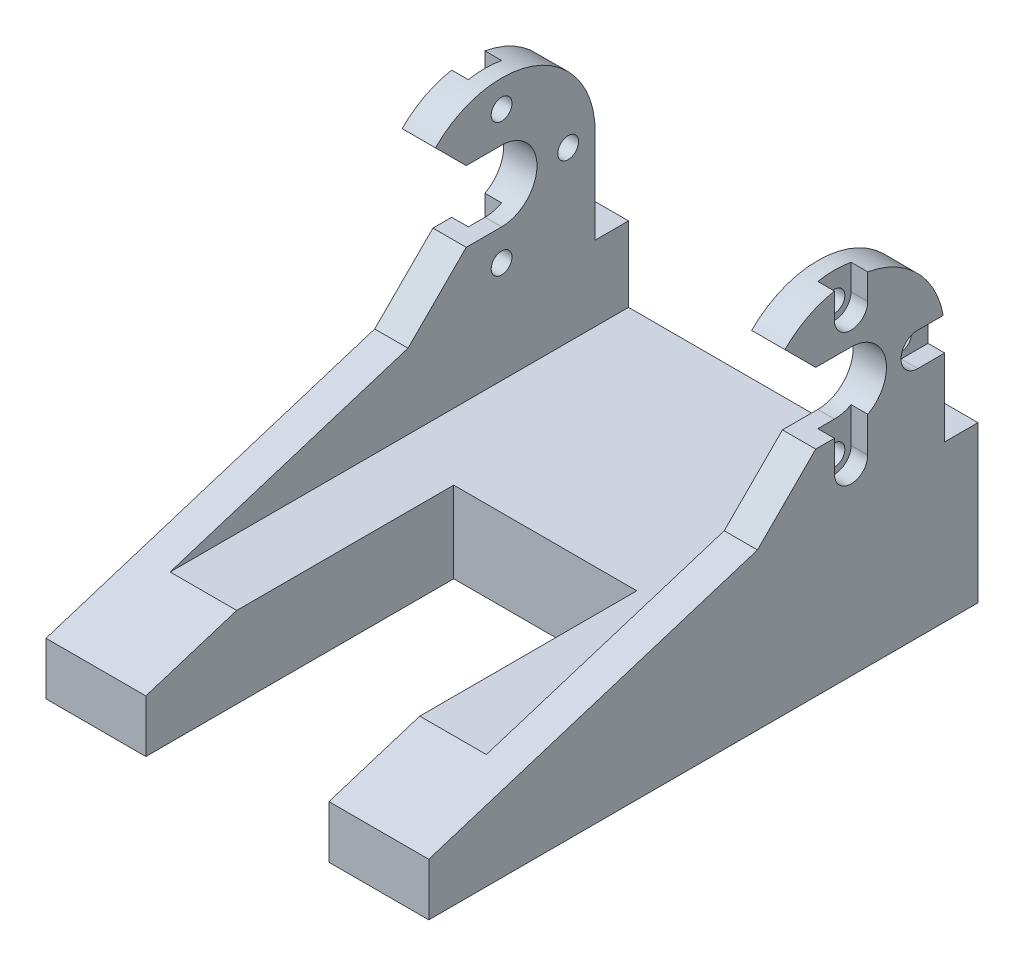
SolidWorks part; units mm, degrees
ref_plane "Front Plane" through (0, 0, 0) normal (0, 0, 1) x (1, 0, 0)
ref_plane "Top Plane" through (0, 0, 0) normal (0, 1, 0) x (1, 0, 0)
ref_plane "Right Plane" through (0, 0, 0) normal (1, 0, 0) x (0, 0, -1)
sketch "Sketch1" plane through (0, 0, 0) normal (0, 0, 1) x (1, 0, 0)
  line L1 (-25, 0) -> (25, 0)
  line L2 (-25, 0) -> (-25, -170)
  line L3 (-25, -170) -> (25, -170)
  line L4 (25, 0) -> (25, -170)
  dimension "D1" = 170
  dimension "D2" = 50
extrude "Boss-Extrude1" add sketch "Sketch1" against normal blind 55
sketch "Sketch2" plane through (0, 0, 0) normal (0, 0, 1) x (1, 0, 0)
  line L0 (25, 0) -> (-25, 0) construction
  line L1 (-17, 0) -> (17, 0)
  line L2 (-17, 0) -> (-17, -27)
  line L3 (-17, -27) -> (17, -27)
  line L4 (17, 0) -> (17, -27)
  line L5 (-25, 0) -> (-25, -170) construction
  dimension "D1" = 8
  dimension "D2" = 34
  dimension "D3" = 27
extrude "Cut-Extrude1" cut sketch "Sketch2" against normal through all
sketch "Sketch3" plane through (25, 0, 0) normal (1, 0, 0) x (0, 0, -1)
  line L0 (0, -170) -> (0, 0) construction
  line L1 (55, -27) -> (0, -27)
  line L2 (55, -27) -> (55, -24)
  line L3 (55, -24) -> (0, -24)
  line L4 (0, -27) -> (0, -24)
  line L5 (55, -170) -> (55, 0) construction
  line L7 (0, 0) -> (10, 0)
  line L8 (0, 0) -> (0, -24)
  line L9 (0, -24) -> (10, -24)
  line L10 (10, 0) -> (10, -24)
  line L11 (55, 0) -> (45, 0)
  line L12 (55, 0) -> (55, -24)
  line L13 (55, -24) -> (45, -24)
  line L14 (45, 0) -> (45, -24)
  circle A0 centre (27.5, -12.75) radius 10.25
  circle A1 centre (27.5, -12.75) radius 4.25
  circle A2 centre (27.5, -12.75) radius 8
  circle A3 centre (27.5, -4.75) radius 1
  circle A4 centre (35.5, -12.75) radius 1
  circle A5 centre (27.5, -20.75) radius 1
  circle A6 centre (19.5, -12.75) radius 1
  point P32 (27.5, -12.75)
  line M7 (0, 0) -> (0, -170)
  line M9 (55, -170) -> (55, 0)
  line M10 (55, 0) -> (0, 0)
  dimension "D2" = 11.25
  dimension "D3" = 27.5
  dimension "D4" = 20.5
  dimension "D7" = 8.5
  dimension "D8" = 16
  dimension "D9" = 4
  dimension "D1" = 3
  dimension "D5" = 10
  dimension "D6" = 10
extrude "Cut-Extrude2" cut sketch "Sketch3" against normal through all contours L14 L3 M10 M9 | L10 L3 M10 M7 | A2 A6 | A2 A6 | A1 | A2 A5 | A2 A5 | A2 A4 | A2 A4 | A2 A3 | A2 A3 region at (25, -12, -50) region at (25, -12, -5) region at (25, -12.75, -27.5) region at (25, -12.75, -35.0645) region at (25, -12.75, -35.913) region at (25, -5.1855, -27.5) region at (25, -4.337, -27.5) region at (25, -21.163, -27.5) region at (25, -20.3145, -27.5) region at (25, -12.75, -19.9355) region at (25, -12.75, -19.087)
sketch "Sketch4" plane through (0, 0, -10) normal (0, 0, 1) x (1, 0, 0)
  line L0 (-25, -24) -> (-17, -24) construction
  line L1 (-17, 0) -> (-19, 0)
  line L2 (-17, 0) -> (-17, -24)
  line L3 (-17, -24) -> (-19, -24)
  line L4 (-19, 0) -> (-19, -24)
  line L5 (0, 0) -> (0, -13.53) construction
  line L6 (19, 0) -> (19, -24)
  line L7 (17, -24) -> (19, -24)
  line L8 (17, 0) -> (17, -24)
  line L9 (17, 0) -> (19, 0)
  dimension "D1" = 2
extrude "Cut-Extrude3" cut sketch "Sketch4" against normal through all
sketch "Sketch5" plane through (25, 0, 0) normal (1, 0, 0) x (0, 0, -1)
  line L1 (10, 0) -> (45, 0)
  line L2 (10, 0) -> (10, -24)
  line L3 (10, -24) -> (45, -24)
  line L4 (45, 0) -> (45, -24)
  line L5 (38.75, -12.75) -> (38.75, -24)
  line L6 (16.25, -12.75) -> (10, -12.75)
  line L7 (16.25, -12.75) -> (16.25, -24)
  line L8 (16.25, -24) -> (10, -24)
  line L9 (10, -12.75) -> (10, -24)
  line L10 (38.75, -12.75) -> (45, -12.75)
  line L11 (38.75, -12.75) -> (38.75, -24)
  line L12 (38.75, -24) -> (45, -24)
  line L13 (45, -12.75) -> (45, -24)
  circle A0 centre (27.5, -12.75) radius 11.25
  line M8 (45, -24) -> (45, 0)
  line M9 (45, 0) -> (10, 0)
  line M10 (10, 0) -> (10, -24)
  dimension "D1" = 22.5
extrude "Cut-Extrude4" cut sketch "Sketch5" against normal through all contours A0 L10 L4 L6 M9 M10 | L7 L6 L2 L3 | L10 L5 L3 M8 region at (25, -0.3725, -27.5) region at (25, -18.375, -13.125) region at (25, -18.375, -41.875)
sketch "Sketch6" plane through (0, 0, 0) normal (0, 0, 1) x (1, 0, 0)
  line L1 (-19, -24) -> (19, -24)
  line L2 (-19, -24) -> (-19, -34)
  line L3 (-19, -34) -> (19, -34)
  line L4 (19, -24) -> (19, -34)
  dimension "D1" = 10
extrude "Cut-Extrude5" cut sketch "Sketch6" against normal through all
sketch "Sketch8" plane through (25, 0, 0) normal (1, 0, 0) x (0, 0, -1)
  line L0 (55, -170) -> (55, -24) construction
  line L1 (0, -170) -> (0, -24) construction
  line L2 (41.75, -132.5) -> (13.25, -132.5)
  line L3 (27.5, -132.5) -> (27.5, -179)
  line L4 (41.75, -179) -> (13.25, -179)
  line L5 (13.25, -132.5) -> (13.25, -179)
  line L7 (41.75, -132.5) -> (41.75, -179)
  line L11 (27.5, -167.75) -> (55, -167.75)
  line L12 (27.5, -167.75) -> (27.5, -170)
  line L13 (27.5, -170) -> (55, -170)
  line L14 (55, -167.75) -> (55, -170)
  line L16 (27.5, -167.75) -> (0, -167.75)
  line L17 (27.5, -167.75) -> (27.5, -170)
  line L18 (27.5, -170) -> (0, -170)
  line L19 (0, -167.75) -> (0, -170)
  circle A0 centre (27.5, -167.75) radius 10.25
  circle A1 centre (27.5, -12.75) radius 10.25
  line M4 (0, -24) -> (0, -170)
  line M5 (0, -170) -> (55, -170)
  line M6 (55, -170) -> (55, -24)
  dimension "D1" = 27.5
  dimension "D2" = 20.5
  dimension "D3" = 155
  dimension "D4" = 14.25
  dimension "D5" = 11.25
  dimension "D6" = 46.5
  dimension "D7" = 13.25
extrude "Cut-Extrude7" cut sketch "Sketch8" against normal through all contours A0 L3 L2 L5 L16 | A0 L11 L7 L2 L3 | L11 L7 M5 M6 | L5 L16 M4 M5 | A0 L16 L5 M5 | A0 L13 L7 L11 | L3 A0 L16 | L11 A0 L3 | L16 A0 L18 L3 | A0 L11 L3 M5 region at (25, -147.5157, -35.1704) region at (25, -147.5157, -19.8296) region at (25, -168.875, -48.375) region at (25, -168.8865, -39.7079) region at (25, -163.3998, -31.8502) region at (25, -163.3998, -23.1498) region at (25, -168.8704, -32.5838) region at (25, -168.8865, -15.2921) region at (25, -168.875, -6.625) region at (25, -168.8704, -22.4162)
sketch "Sketch9" plane through (0, 0, 0) normal (0, 0, 1) x (1, 0, 0)
  line L0 (-25, -167.75) -> (25, -167.75) construction
  line L1 (17, -167.75) -> (-17, -167.75)
  line L2 (17, -167.75) -> (17, -132.5)
  line L3 (17, -132.5) -> (-17, -132.5)
  line L4 (-17, -167.75) -> (-17, -132.5)
  line L5 (-25, -132.5) -> (25, -132.5) construction
  line L7 (-25, -24) -> (-25, -167.75) construction
  line L9 (25, -167.75) -> (25, -24) construction
  dimension "D1" = 8
  dimension "D2" = 8
extrude "Cut-Extrude8" cut sketch "Sketch9" against normal through all
sketch "Sketch11" plane through (25, 0, 0) normal (1, 0, 0) x (0, 0, -1)
  line L0 (27.5, -157.5) -> (27.5, -147.5)
  line L2 (27.5, -147.5) -> (55, -147.5)
  line L3 (27.5, -147.5) -> (27.5, -167.75)
  line L4 (27.5, -167.75) -> (55, -167.75)
  line L5 (55, -147.5) -> (55, -167.75)
  line L6 (27.5, -147.5) -> (0, -147.5)
  line L7 (27.5, -147.5) -> (27.5, -167.75)
  line L8 (27.5, -167.75) -> (0, -167.75)
  line L9 (0, -147.5) -> (0, -167.75)
  circle A0 centre (27.5, -167.75) radius 10.25
  arc A1 (38.75, -12.75) -> (16.25, -12.75) centre (27.5, -12.75) ccw construction
  line M1 (0, -167.75) -> (13.25, -167.75)
  line M2 (13.25, -167.75) -> (13.25, -132.5)
  line M4 (41.75, -132.5) -> (41.75, -167.75)
  line M5 (41.75, -167.75) -> (55, -167.75)
  line M6 (55, -167.75) -> (55, -24)
  line M12 (0, -24) -> (0, -167.75)
  dimension "D1" = 155
  dimension "D2" = 20.5
  dimension "D3" = 10
extrude "Cut-Extrude9" cut sketch "Sketch11" against normal through all contours A0 L0 L6 L8 M2 | A0 L4 L2 L0 M4 | L2 M4 M5 M6 | L6 M2 M12 M1 region at (25, -155.3124, -19.2638) region at (25, -155.3124, -35.7362) region at (25, -157.625, -48.375) region at (25, -157.625, -6.625)
sketch "Sketch12" plane through (25, 0, 0) normal (1, 0, 0) x (0, 0, -1)
  line L1 (13.25, -132.5) -> (41.75, -132.5)
  line L2 (13.25, -132.5) -> (13.25, -147.5)
  line L3 (13.25, -147.5) -> (41.75, -147.5)
  line L4 (41.75, -132.5) -> (41.75, -147.5)
extrude "Boss-Extrude2" add sketch "Sketch12" against normal blind 8
ref_plane "Plane1" through (0, 0, 0) normal (1, 0, 0) x (0, 0, -1)
mirror "Mirror1" about plane through (0, 0, 0) normal (1, 0, 0) of "Boss-Extrude2"
sketch "Sketch14" plane through (0, 0, 0) normal (0, 0, 1) x (1, 0, 0)
  line L0 (17, -148.55) -> (17, -158.75) construction
  line L1 (-17, -132.5) -> (17, -132.5)
  line L2 (-17, -132.5) -> (-17, -147.5)
  line L3 (-17, -147.5) -> (17, -147.5)
  line L4 (17, -132.5) -> (17, -147.5)
  line L5 (-17, -147.5) -> (17, -147.5)
  line L6 (-17, -147.5) -> (-17, -157.75)
  line L7 (-17, -157.75) -> (17, -157.75)
  line L8 (17, -147.5) -> (17, -157.75)
  line M11 (-17, -147.5) -> (-17, -132.5)
  line M12 (-17, -132.5) -> (17, -132.5)
  line M13 (17, -132.5) -> (17, -147.5)
  dimension "D1" = 10.25
extrude "Boss-Extrude3" add sketch "Sketch14" against normal blind 13.25 contours L3 M11 M13 M12 | L8 L3 L6 L7 region at (0, -140, 0) region at (0, -152.625, 0)
ref_plane "Plane2" through (0, 0, -27.5) normal (0, 0, 1) x (1, 0, 0)
mirror "Mirror2" about plane through (0, 0, -27.5) normal (0, 0, 1) of "Boss-Extrude3"
sketch "Sketch16" plane through (25, 0, 0) normal (1, 0, 0) x (0, 0, -1)
  line L0 (41.75, -132.5) -> (13.25, -132.5) construction
  line L1 (13.25, -132.5) -> (13.25, -147.5) construction
  circle A1 centre (16.5, -135.75) radius 2.5
  circle A2 centre (16.5, -135.75) radius 4.5
  circle A3 centre (38.5, -135.75) radius 4.5
  dimension "D1" = 3.25
  dimension "D2" = 3.25
  dimension "D3" = 2
extrude "Cut-Extrude13" cut sketch "Sketch16" against normal blind 8 contours A1 | A2 A1 | A3 region at (25, -135.75, -16.5) region at (25, -135.75, -12.1273) region at (25, -135.75, -38.5)
mirror "Mirror3" about plane through (0, 0, 0) normal (1, 0, 0) of "Cut-Extrude13"
sketch "Sketch17" plane through (25, 0, 0) normal (1, 0, 0) x (0, 0, -1)
  line L0 (55, -147.5) -> (55, -24) construction
  line L1 (27.5, -1.5) -> (55, -1.5)
  line L2 (27.5, -1.5) -> (27.5, -51.5)
  line L3 (27.5, -51.5) -> (55, -51.5)
  line L4 (55, -1.5) -> (55, -51.5)
  line L8 (55, -51.5) -> (0, -51.5)
  line L9 (55, -51.5) -> (55, -157.75)
  line L10 (55, -157.75) -> (0, -157.75)
  line L11 (0, -51.5) -> (0, -157.75)
  arc A0 (38.75, -12.75) -> (16.25, -12.75) centre (27.5, -12.75) ccw construction
  circle M2 centre (16.5, -135.75) radius 4.5
  circle M3 centre (38.5, -135.75) radius 4.5
  line M4 (0, -147.5) -> (55, -147.5)
  line M5 (55, -147.5) -> (55, -24)
  line M11 (0, -24) -> (0, -147.5)
  dimension "D1" = 50
extrude "Cut-Extrude15" cut sketch "Sketch17" against normal through all contours L3 L8 M11 M4 M5 M2 M3 | L11 L10 L9 M4 | M3 | M2 region at (25, -98.6049, -27.5) region at (25, -152.625, -27.5) region at (25, -135.75, -16.5) region at (25, -135.75, -38.5)
sketch "Sketch18" plane through (25, 0, 0) normal (1, 0, 0) x (0, 0, -1)
  line L1 (38.75, -24) -> (-71.25, -24)
  line L2 (38.75, -24) -> (38.75, -51.5)
  line L3 (38.75, -51.5) -> (-71.25, -51.5)
  line L4 (-71.25, -24) -> (-71.25, -51.5)
  line L6 (38.75, -24) -> (68.75, -24)
  line L7 (38.75, -24) -> (38.75, -51.5)
  line L8 (38.75, -51.5) -> (68.75, -51.5)
  line L9 (68.75, -24) -> (68.75, -51.5)
  line M8 (0, -24) -> (0, -51.5)
  line M9 (0, -51.5) -> (55, -51.5)
  line M10 (55, -51.5) -> (55, -24)
  line M11 (55, -24) -> (38.75, -24)
  line M15 (16.25, -24) -> (0, -24)
  dimension "D1" = 110
  dimension "D2" = 30
extrude "Boss-Extrude4" add sketch "Sketch18" against normal blind 50 contours L1 L4 L3 M8 | L9 L6 L8 M10 | L2 L1 M15 M8 M9 | L2 M11 M9 M10 region at (25, -37.75, -19.375) region at (25, -37.75, -46.875) region at (25, -37.75, -61.875) region at (25, -37.75, 35.625)
sketch "Sketch19" plane through (0, 0, 71.25) normal (0, 0, 1) x (1, 0, 0)
  line L1 (-19, -24) -> (19, -24)
  line L2 (-19, -24) -> (-19, -31)
  line L3 (-19, -31) -> (19, -31)
  line L4 (19, -24) -> (19, -31)
  dimension "D1" = 7
extrude "Cut-Extrude16" cut sketch "Sketch19" against normal through all
sketch "Sketch20" plane through (25, 0, 0) normal (1, 0, 0) x (0, 0, -1)
  line L1 (-71.25, -24) -> (68.75, -24)
  line L2 (-71.25, -24) -> (-71.25, -51.5)
  line L3 (-71.25, -51.5) -> (68.75, -51.5)
  line L4 (68.75, -24) -> (68.75, -51.5)
  line L5 (16.25, -24) -> (-13.75, -24)
  line L6 (16.25, -24) -> (16.25, -51.5)
  line L7 (16.25, -51.5) -> (-13.75, -51.5)
  line L8 (-13.75, -24) -> (-13.75, -51.5)
  line L10 (-13.75, -51.5) -> (-71.25, -51.5)
  line L11 (-13.75, -51.5) -> (-13.75, -24)
  line L12 (-13.75, -24) -> (-71.25, -24)
  line L13 (-71.25, -51.5) -> (-71.25, -24)
  line M8 (-71.25, -24) -> (-71.25, -51.5)
  line M9 (-71.25, -51.5) -> (68.75, -51.5)
  dimension "D1" = 30
extrude "Cut-Extrude17" cut sketch "Sketch20" against normal through all contours L8 L1 M8 M9 region at (25, -37.75, 42.5)
sketch "Sketch21" plane through (25, 0, 0) normal (1, 0, 0) x (0, 0, -1)
  line L0 (16.25, -24) -> (-13.75, -51.5)
  line L1 (16.25, -24) -> (-13.75, -24)
  line L2 (16.25, -24) -> (16.25, -51.5)
  line L3 (16.25, -51.5) -> (-13.75, -51.5)
  line L4 (-13.75, -24) -> (-13.75, -51.5)
  line M6 (16.25, -24) -> (-13.75, -24)
  line M7 (-13.75, -24) -> (-13.75, -51.5)
extrude "Cut-Extrude18" cut sketch "Sketch21" against normal through all contours L0 M6 M7 region at (25, -33.1667, 3.75)
sketch "Sketch22" plane through (25, 0, 0) normal (1, 0, 0) x (0, 0, -1)
  line L3 (68.75, -51.5) -> (-13.75, -51.5)
  line L4 (68.75, -51.5) -> (68.75, -54)
  line L5 (68.75, -54) -> (-13.75, -54)
  line L6 (-13.75, -51.5) -> (-13.75, -54)
  dimension "D1" = 2.5
extrude "Boss-Extrude5" add sketch "Sketch22" against normal blind 50
sketch "Sketch24" plane through (25, 0, 0) normal (1, 0, 0) x (0, 0, -1)
  line L1 (68.75, -24) -> (46.75, -24)
  line L2 (68.75, -24) -> (68.75, -41)
  line L3 (68.75, -41) -> (46.75, -41)
  line L4 (46.75, -24) -> (46.75, -41)
  dimension "D1" = 17
  dimension "D2" = 22
extrude "Cut-Extrude19" cut sketch "Sketch24" against normal through all
sketch "Sketch25" plane through (0, -31, 0) normal (0, 1, 0) x (1, 0, 0)
  line L1 (-19, 46.75) -> (19, 46.75)
  line L2 (-19, 46.75) -> (-19, 8.6136)
  line L3 (-19, 8.6136) -> (19, 8.6136)
  line L4 (19, 46.75) -> (19, 8.6136)
extrude "Cut-Extrude20" cut sketch "Sketch25" against normal blind 10
sketch "Sketch27" plane through (0, -41, 0) normal (0, 1, 0) x (1, 0, 0)
  line L0 (-25, 68.75) -> (25, 68.75) construction
  line L1 (19, 8.6136) -> (-19, 8.6136)
  line L2 (19, 8.6136) -> (19, 68.75)
  line L3 (19, 68.75) -> (-19, 68.75)
  line L4 (-19, 8.6136) -> (-19, 68.75)
extrude "Boss-Extrude6" add sketch "Sketch27" along normal blind 8.6
sketch "Sketch29" plane through (0, 0, -8.6136) normal (0, 0, -1) x (-1, 0, 0)
  line L1 (-19, -31) -> (19, -31)
  line L2 (-19, -31) -> (-19, -32.4)
  line L3 (-19, -32.4) -> (19, -32.4)
  line L4 (19, -31) -> (19, -32.4)
extrude "Cut-Extrude21" cut sketch "Sketch29" against normal through all
sketch "Sketch30" plane through (-25, 0, 0) normal (-1, 0, 0) x (0, 0, 1)
  line L0 (-68.75, -32.4) -> (-68.75, -41) construction
  line L1 (-38.75, -24) -> (31.25, -24)
  line L2 (-38.75, -24) -> (-38.75, -53.9144)
  line L3 (-38.75, -53.9144) -> (31.25, -53.9144)
  line L4 (31.25, -24) -> (31.25, -53.9144)
  line L5 (-16.25, -24) -> (31.25, -38.9572)
  line L6 (31.25, -38.9572) -> (31.25, -53.9144)
  line L7 (-16.25, -24) -> (-16.25, -32.4)
  line L8 (-46.75, -32.4) -> (-7.0864, -32.4) construction
  line L9 (-16.25, -32.4) -> (-7.0864, -32.4)
  line L10 (-7.0864, -32.4) -> (-16.25, -24)
  line M5 (13.75, -54) -> (13.75, -51.5)
  line M6 (13.75, -51.5) -> (-16.25, -24)
  dimension "D1" = 100
extrude "Boss-Extrude7" add sketch "Sketch30" against normal blind 50 contours L5 L3 L4 M6 M5 | L7 L9 L10 region at (-25, -40.9436, 13.5151)
sketch "Sketch31" plane through (0, 0, -68.75) normal (0, 0, -1) x (-1, 0, 0)
  line L1 (-19, -24) -> (19, -24)
  line L2 (-19, -24) -> (-19, -41)
  line L3 (-19, -41) -> (19, -41)
  line L4 (19, -24) -> (19, -41)
extrude "Cut-Extrude22" cut sketch "Sketch31" against normal through all
sketch "Sketch32" plane through (25, 0, 0) normal (1, 0, 0) x (0, 0, -1)
  line L0 (-31.25, -38.9572) -> (-31.25, -53.9144) construction
  line L1 (68.75, -54) -> (-31.25, -54)
  line L2 (68.75, -54) -> (68.75, -51)
  line L3 (68.75, -51) -> (-31.25, -51)
  line L4 (-31.25, -54) -> (-31.25, -51)
  dimension "D1" = 3
extrude "Cut-Extrude23" cut sketch "Sketch32" against normal through all
sketch "Sketch33" plane through (0, -41, 0) normal (0, 1, 0) x (1, 0, 0)
  line L0 (19, -31.25) -> (-19, -31.25) construction
  line L1 (11, -31.25) -> (-11, -31.25)
  line L2 (11, -31.25) -> (11, 13.75)
  line L3 (11, 13.75) -> (-11, 13.75)
  line L4 (-11, -31.25) -> (-11, 13.75)
  line L6 (-25, 68.75) -> (-10, 68.75)
  line L7 (-25, 68.75) -> (-25, 46.75)
  line L8 (-25, 46.75) -> (-10, 46.75)
  line L9 (-10, 68.75) -> (-10, 46.75)
  line L10 (25, 68.75) -> (10, 68.75)
  line L11 (25, 68.75) -> (25, 46.75)
  line L12 (25, 46.75) -> (10, 46.75)
  line L13 (10, 68.75) -> (10, 46.75)
  line L15 (19, 16.25) -> (19, -31.25) construction
  line L16 (-19, -31.25) -> (-19, 46.75) construction
  line L18 (-10, 68.75) -> (10, 68.75)
  line L19 (-10, 68.75) -> (-10, 58.75)
  line L20 (-10, 58.75) -> (10, 58.75)
  line L21 (10, 68.75) -> (10, 58.75)
  line M10 (-25, 46.75) -> (-19, 46.75)
  line M12 (-19, -31.25) -> (19, -31.25)
  line M14 (19, 46.75) -> (25, 46.75)
  line M15 (25, 46.75) -> (25, 68.75)
  line M16 (25, 68.75) -> (-25, 68.75)
  line M17 (-25, 68.75) -> (-25, 46.75)
  dimension "D1" = 8
  dimension "D2" = 8
  dimension "D3" = 45
  dimension "D4" = 15
  dimension "D5" = 15
  dimension "D6" = 10
extrude "Cut-Extrude24" cut sketch "Sketch33" against normal through all contours L9 L8 M16 M17 M10 | L13 L12 M16 M14 M15 | L9 L20 L13 M16 | L4 L2 L3 M12 region at (0, -41, 8.75) region at (-17.5, -41, -57.75) region at (0, -41, -63.75) region at (17.5, -41, -57.75)
sketch "Sketch34" plane through (0, -41, 0) normal (0, 1, 0) x (1, 0, 0)
  line L0 (-10, 58.75) -> (10, 58.75) construction
  line L1 (-4, 58.75) -> (4, 58.75)
  line L2 (-4, 58.75) -> (-4, 46.75)
  line L3 (-4, 46.75) -> (4, 46.75)
  line L4 (4, 58.75) -> (4, 46.75)
  line L5 (-10, 58.75) -> (-10, 46.75) construction
  line L6 (10, 58.75) -> (10, 46.75) construction
  dimension "D1" = 6
  dimension "D2" = 6
  dimension "D3" = 12
extrude "Cut-Extrude25" cut sketch "Sketch34" against normal through all
sketch "Sketch36" plane through (0, -41, 0) normal (0, 1, 0) x (1, 0, 0)
  line L1 (19, -31.25) -> (-19, -31.25)
  line L2 (19, -31.25) -> (19, 58.75)
  line L3 (19, 58.75) -> (-19, 58.75)
  line L4 (-19, -31.25) -> (-19, 58.75)
  line L5 (-4, 58.75) -> (4, 58.75)
  line L6 (-4, 58.75) -> (-4, 46.75)
  line L7 (-4, 46.75) -> (4, 46.75)
  line L8 (4, 58.75) -> (4, 46.75)
  line L9 (10, 58.75) -> (19, 58.75)
  line L10 (10, 58.75) -> (10, 46.75)
  line L11 (10, 46.75) -> (19, 46.75)
  line L12 (19, 58.75) -> (19, 46.75)
  line L13 (-10, 58.75) -> (-19, 58.75)
  line L14 (-10, 58.75) -> (-10, 46.75)
  line L15 (-10, 46.75) -> (-19, 46.75)
  line L16 (-19, 58.75) -> (-19, 46.75)
  line L17 (-11, 13.75) -> (11, 13.75)
  line L18 (-11, 13.75) -> (-11, -31.25)
  line L19 (-11, -31.25) -> (11, -31.25)
  line L20 (11, 13.75) -> (11, -31.25)
  line M1 (4, 46.75) -> (-4, 46.75)
  line M2 (-4, 46.75) -> (-4, 58.75)
  line M3 (-4, 58.75) -> (-10, 58.75)
  line M4 (-10, 58.75) -> (-10, 46.75)
  line M5 (-10, 46.75) -> (-19, 46.75)
  line M6 (-19, 46.75) -> (-19, -31.25)
  line M7 (-19, -31.25) -> (-11, -31.25)
  line M8 (-11, -31.25) -> (-11, 13.75)
  line M9 (-11, 13.75) -> (11, 13.75)
  line M10 (11, 13.75) -> (11, -31.25)
  line M11 (11, -31.25) -> (19, -31.25)
  line M12 (19, -31.25) -> (19, 46.75)
  line M13 (19, 46.75) -> (10, 46.75)
  line M14 (10, 46.75) -> (10, 58.75)
  line M15 (10, 58.75) -> (4, 58.75)
  line M16 (4, 58.75) -> (4, 46.75)
extrude "Boss-Extrude8" add sketch "Sketch36" along normal blind 8 contours M16 M1 M2 M3 M4 M5 M6 M7 M8 M9 M10 M11 M12 M13 M14 M15 region at (0, -41, -18.522)
sketch "Sketch37" plane through (25, 0, 0) normal (1, 0, 0) x (0, 0, -1)
  line L0 (-31.25, -38.9572) -> (-31.25, -51) construction
  line L1 (58.75, -51) -> (-31.25, -51)
  line L2 (58.75, -51) -> (58.75, -42)
  line L3 (58.75, -42) -> (-31.25, -42)
  line L4 (-31.25, -51) -> (-31.25, -42)
  line L5 (-31.25, -38.9572) -> (-12.3315, -33)
  line L6 (-12.3315, -33) -> (-31.25, -33)
  line L7 (-12.3315, -33) -> (-12.3315, -38.9572)
  line L8 (-12.3315, -38.9572) -> (-31.25, -38.9572)
  line L9 (-31.25, -33) -> (-31.25, -38.9572)
  line L11 (58.75, -42) -> (46.75, -42)
  line L12 (58.75, -42) -> (58.75, -51)
  line L13 (58.75, -51) -> (46.75, -51)
  line L14 (46.75, -42) -> (46.75, -51)
  line M7 (-31.25, -51) -> (46.75, -51)
  line M8 (46.75, -51) -> (46.75, -24)
  line M13 (16.25, -24) -> (-31.25, -38.9572)
  line M14 (-31.25, -38.9572) -> (-31.25, -51)
  dimension "D1" = 9
extrude "Cut-Extrude27" cut sketch "Sketch37" against normal through all contours L3 M8 M14 M7 | L6 L9 M13 | L2 L3 L1 M8 region at (25, -34.9857, 24.9438) region at (25, -46.5, -52.75) region at (25, -46.5, -7.75)
fillet "Fillet1" radius 10 2 edges at (-7, -42, -58.75) (7, -42, -58.75)
sketch "Sketch38" plane through (0, 0, 0) normal (0, 1, 0) x (1, 0, 0)
  line L6 (-11, -31.25) -> (-25, -31.25) construction
  line L7 (-25, 46.75) -> (-23, 46.75)
  line L8 (-25, 46.75) -> (-25, -31.25)
  line L9 (-25, -31.25) -> (-23, -31.25)
  line L10 (-23, 46.75) -> (-23, -31.25)
  line L11 (25, -31.25) -> (11, -31.25) construction
  line L12 (25, 46.75) -> (23, 46.75)
  line L13 (25, 46.75) -> (25, -31.25)
  line L14 (25, -31.25) -> (23, -31.25)
  line L15 (23, 46.75) -> (23, -31.25)
  line L17 (-23, -31.25) -> (23, -31.25)
  line L18 (-23, -31.25) -> (-23, -23.25)
  line L19 (-23, -23.25) -> (23, -23.25)
  line L20 (23, -31.25) -> (23, -23.25)
  dimension "D1" = 2
  dimension "D2" = 2
  dimension "D3" = 8
extrude "Cut-Extrude29" cut sketch "Sketch38" against normal through all both and the other way through all contours L10 L7 L8 L9 | L12 L15 L14 L13 | L19 L10 L17 L15 region at (-24, 0, -7.75) region at (0, 0, 27.25) region at (24, 0, -7.75)
sketch "Sketch39" plane through (23, 0, 0) normal (1, 0, 0) x (0, 0, -1)
  line L0 (46.75, -24) -> (38.75, -24) construction
  line L1 (42.75, -24) -> (64.9734, -24)
  line L2 (42.75, -24) -> (42.75, -43.4413)
  line L3 (42.75, -43.4413) -> (64.9734, -43.4413)
  line L4 (64.9734, -24) -> (64.9734, -43.4413)
extrude "Cut-Extrude30" cut sketch "Sketch39" against normal through all
sketch "Sketch41" plane through (0, -42, 0) normal (0, -1, 0) x (1, 0, 0)
  line L1 (-23, 23.25) -> (23, 23.25)
  line L2 (-23, 23.25) -> (-23, -42.75)
  line L3 (-23, -42.75) -> (23, -42.75)
  line L4 (23, 23.25) -> (23, -42.75)
  line L5 (-11, 23.25) -> (11, 23.25)
  line L6 (-11, 23.25) -> (-11, -13.75)
  line L7 (-11, -13.75) -> (11, -13.75)
  line L8 (11, 23.25) -> (11, -13.75)
  line M1 (-23, 23.25) -> (-23, -42.75)
  line M2 (-23, -42.75) -> (23, -42.75)
  line M3 (23, -42.75) -> (23, 23.25)
  line M4 (23, 23.25) -> (11, 23.25)
  line M5 (11, 23.25) -> (11, -13.75)
  line M6 (11, -13.75) -> (-11, -13.75)
  line M7 (-11, -13.75) -> (-11, 23.25)
  line M8 (-11, 23.25) -> (-23, 23.25)
extrude "Boss-Extrude9" add sketch "Sketch41" along normal blind 0.75 contours M8 M1 M2 M3 M4 M5 M6 M7 region at (0, -42, -15.0619)
sketch "Sketch42" plane through (23, 0, 0) normal (1, 0, 0) x (0, 0, -1)
  line L0 (16.25, -24) -> (27.5, -12.75)
  line L1 (27.5, -12.75) -> (19.545, -4.795)
  line L2 (19.545, -4.795) -> (8.295, -16.045)
  line L3 (8.295, -16.045) -> (16.25, -24)
  arc A0 (38.75, -12.75) -> (16.25, -12.75) centre (27.5, -12.75) ccw construction
extrude "Cut-Extrude31" cut sketch "Sketch42" against normal through all
sketch "Sketch44" plane through (23, 0, 0) normal (1, 0, 0) x (0, 0, -1)
  circle A0 centre (27.5, -4.75) radius 1.25
  circle A1 centre (27.5, -12.75) radius 8
  circle A2 centre (35.5, -12.75) radius 1.25
  circle A3 centre (27.5, -20.75) radius 1.25
  circle A4 centre (19.5, -12.75) radius 1.25
  point P15 (27.5, -12.75)
  circle M11 centre (35.5, -12.75) radius 1
  circle M12 centre (27.5, -4.75) radius 1
  circle M13 centre (27.5, -20.75) radius 1
  dimension "D1" = 2.5
  dimension "D2" = 4
extrude "Cut-Extrude32" cut sketch "Sketch44" against normal through all contours A1 A2 M11 | A1 A2 M11 | A0 A1 M12 | A1 A0 M12 | A1 A3 M13 | A1 A3 M13 region at (23, -4.7978, -28.7207) region at (23, -4.8564, -26.3816) region at (23, -11.8531, -36.3294) region at (23, -11.6316, -35.3936) region at (23, -19.5276, -27.5) region at (23, -20.699, -26.3738)
sketch "Sketch45" plane through (23, 0, 0) normal (1, 0, 0) x (0, 0, -1)
  line L0 (27.5, -4.75) -> (27.5, 0.25) construction
  line L9 (25.5, -4.75) -> (25.5, 0.25)
  line L10 (29.5, -4.75) -> (29.5, 0.25)
  line L11 (35.5, -12.75) -> (40.5, -12.75) construction
  line L12 (35.5, -10.75) -> (40.5, -10.75)
  line L13 (35.5, -14.75) -> (40.5, -14.75)
  line L17 (19.5, -12.75) -> (14.5, -12.75) construction
  line L18 (19.5, -14.75) -> (14.5, -14.75)
  line L19 (19.5, -10.75) -> (14.5, -10.75)
  line L21 (29.5, -20.75) -> (25.5, -20.75)
  line L22 (29.5, -20.75) -> (29.5, -14.3206)
  line L23 (29.5, -14.3206) -> (25.5, -14.3206)
  line L24 (25.5, -20.75) -> (25.5, -14.3206)
  line L27 (27.5, -20.75) -> (27.5, -25.75) construction
  line L28 (29.5, -20.75) -> (29.5, -25.75)
  line L29 (25.5, -20.75) -> (25.5, -25.75)
  line L30 (27.5, -20.75) -> (27.5, -25.75) construction
  line L31 (29.5, -20.75) -> (29.5, -25.75)
  line L32 (25.5, -20.75) -> (25.5, -25.75)
  circle A1 centre (27.5, -12.75) radius 8
  arc A8 (25.5, -4.75) -> (29.5, -4.75) centre (27.5, -4.75) ccw
  arc A9 (29.5, 0.25) -> (25.5, 0.25) centre (27.5, 0.25) ccw
  arc A10 (35.5, -10.75) -> (35.5, -14.75) centre (35.5, -12.75) ccw
  arc A11 (40.5, -14.75) -> (40.5, -10.75) centre (40.5, -12.75) ccw
  arc A12 (29.5, -20.75) -> (25.5, -20.75) centre (27.5, -20.75) ccw
  arc A14 (19.5, -14.75) -> (19.5, -10.75) centre (19.5, -12.75) ccw
  arc A15 (14.5, -10.75) -> (14.5, -14.75) centre (14.5, -12.75) ccw
  circle A16 centre (27.5, -20.75) radius 2
  arc A21 (29.5, -20.75) -> (25.5, -20.75) centre (27.5, -20.75) ccw
  arc A22 (25.5, -25.75) -> (29.5, -25.75) centre (27.5, -25.75) ccw
  point P7 (27.5, -2.25)
  point P16 (27.125, -13.125)
  point P17 (27.5, -12.75)
  point P18 (38, -12.75)
  point P25 (27.5, -23.25)
  point P32 (17, -12.75)
  point P37 (27.5, -12.75)
  point P44 (27.5, -23.25)
  point P52 (27.5, -23.25)
  point P59 (27.5, -23.25)
  circle M1 centre (35.5, -12.75) radius 1.25
  circle M2 centre (27.5, -4.75) radius 1.25
  circle M3 centre (27.5, -20.75) radius 1.25
  arc M4 (38.75, -12.75) -> (19.545, -4.795) centre (27.5, -12.75) ccw
  arc M6 (24.4948, -9.7448) -> (24.4948, -15.7552) centre (27.5, -12.75) cw
  line M13 (38.75, -24) -> (38.75, -12.75)
  dimension "D1" = 5
  dimension "D2" = 2
  dimension "D3" = 4
ref_plane "Plane3" through (0, 0, 0) normal (1, 0, 0) x (0, 0, -1)
extrude "Cut-Extrude33" cut sketch "Sketch45" against normal blind 2 contours L9 A8 A1 L10 M2 M4 | A1 A8 M2 | L12 A10 A1 L13 M1 M13 M4 | A1 A10 M1 | L21 A16 M3 | A12 A1 L22 L24 M6 | A1 A12 M3 | L21 L24 L23 L22 region at (23, -2.947, -27.5) region at (23, -4.9582, -25.8919) region at (23, -12.7667, -37.3185) region at (23, -11.1419, -35.2918) region at (23, -18.0455, -27.5) region at (23, -20.7947, -25.875) region at (23, -18.794, -27.5)
mirror "Mirror4" about plane through (0, 0, 0) normal (1, 0, 0) of "Cut-Extrude33"
sketch "Sketch47" plane through (23, 0, 0) normal (1, 0, 0) x (0, 0, -1)
  line L1 (27.5, -17) -> (17.8705, -17)
  line L2 (27.5, -17) -> (27.5, -8.5)
  line L3 (27.5, -8.5) -> (17.8705, -8.5)
  line L4 (17.8705, -17) -> (17.8705, -8.5)
  circle A0 centre (27.5, -12.75) radius 4.25
  line M3 (19.545, -4.795) -> (24.4948, -9.7448)
  arc M4 (24.4948, -9.7448) -> (29.5, -16.5) centre (27.5, -12.75) cw
  line M7 (25.5, -20.75) -> (25.5, -16.5)
  arc M8 (25.5, -16.5) -> (24.4948, -15.7552) centre (27.5, -12.75) cw
  line M9 (24.4948, -15.7552) -> (16.25, -24)
extrude "Cut-Extrude34" cut sketch "Sketch47" against normal through all contours L2 A0 M4 | A0 L2 M4 M8 | A0 L3 L4 L1 M3 M9 | L3 M4 M3 | L1 M7 M8 M9 | A0 L1 M7 region at (23, -12.75, -25.6962) region at (23, -16.8516, -25.9939) region at (23, -12.75, -29.3038) region at (23, -16.5697, -24.5181) region at (23, -8.883, -24.7656) region at (23, -12.75, -20.8004)
